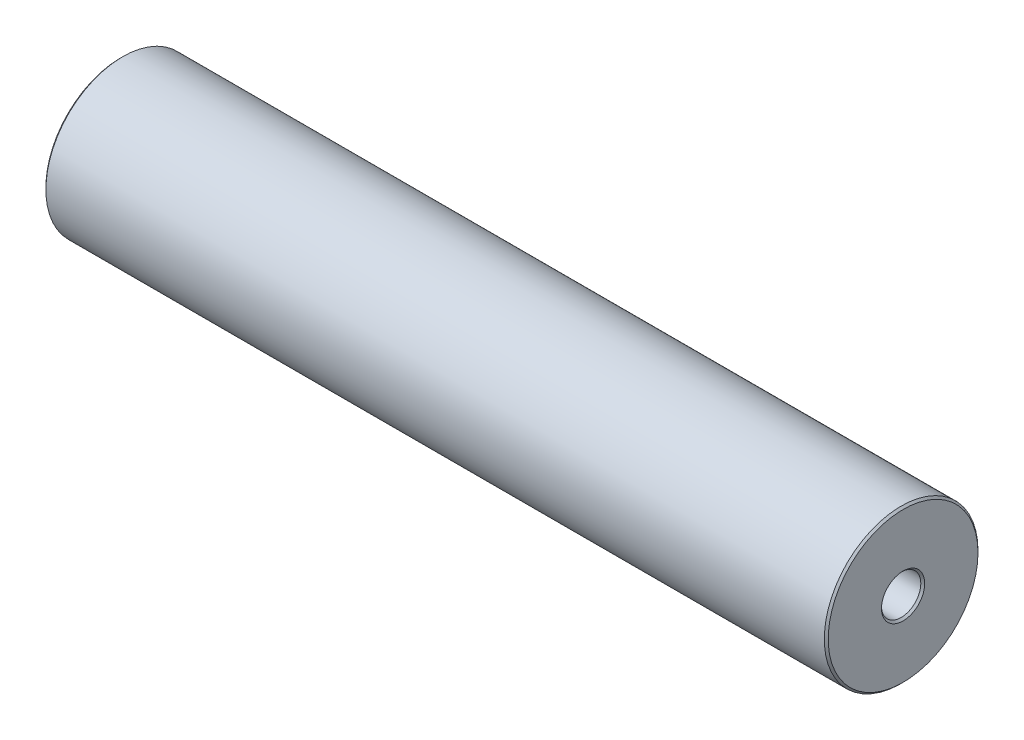
SolidWorks part; units mm, degrees
material "6061-T6 (SS)"
ref_plane "Front Plane" through (0, 0, 0) normal (0, 0, 1) x (1, 0, 0)
ref_plane "Top Plane" through (0, 0, 0) normal (0, 1, 0) x (1, 0, 0)
ref_plane "Right Plane" through (0, 0, 0) normal (1, 0, 0) x (0, 0, -1)
sketch "Sketch2" plane through (0, 0, 0) normal (1, 0, 0) x (0, 0, -1)
  circle A0 centre (0, 0) radius 9.9809
  dimension "D1" = 19.9619
extrude "Boss-Extrude1" add sketch "Sketch2" along normal mid plane 101.6
hole_wizard "1/4-20 Tapped Hole1" positions "3DSketch1" profile "Sketch3" tap size "1/4-20" standard "ANSI Inch"
sketch3d "3DSketch1"
  line L0 (50.8, 0, 0) -> (-50.8, 0, 0) construction
  point P0 (50.8, 0, 0)
  point P4 (-50.8, 0, 0)
sketch "Sketch3" plane through (50.8, 0, 0) normal (0, 1, 0) x (0, 0, -1)
  line L0 (0, 0) -> (0, 18.0438)
  line L1 (0, 18.0438) -> (2.5527, 16.51)
  line L2 (2.5527, 16.51) -> (2.5527, 0)
  line L5 (2.5527, 0) -> (0, 0)
  line L10 (0, 18.0438) -> (-2.5527, 16.51) construction
  line L11 (0, -6.35) -> (0, 107.95) construction
  dimension "Tap Drill Dia." = 5.1054
  dimension "Tap Drill Depth" = 16.51
  dimension "Drill Angle" = 118
cosmetic thread "Hole Thread1" parameters "D1"=12.7, "D2"=6.35
cosmetic thread "Hole Thread2" parameters "D1"=12.7, "D2"=6.35
chamfer "Chamfer1" distance 0.254 angle 45 4 edges at (50.8, 0, -9.9809) (50.8, 0, -2.5527) (-50.8, 0, -9.9809) (-50.8, 0, 2.5527)
equation "\"D1@Sketch2\"=20mm-0.0015"
